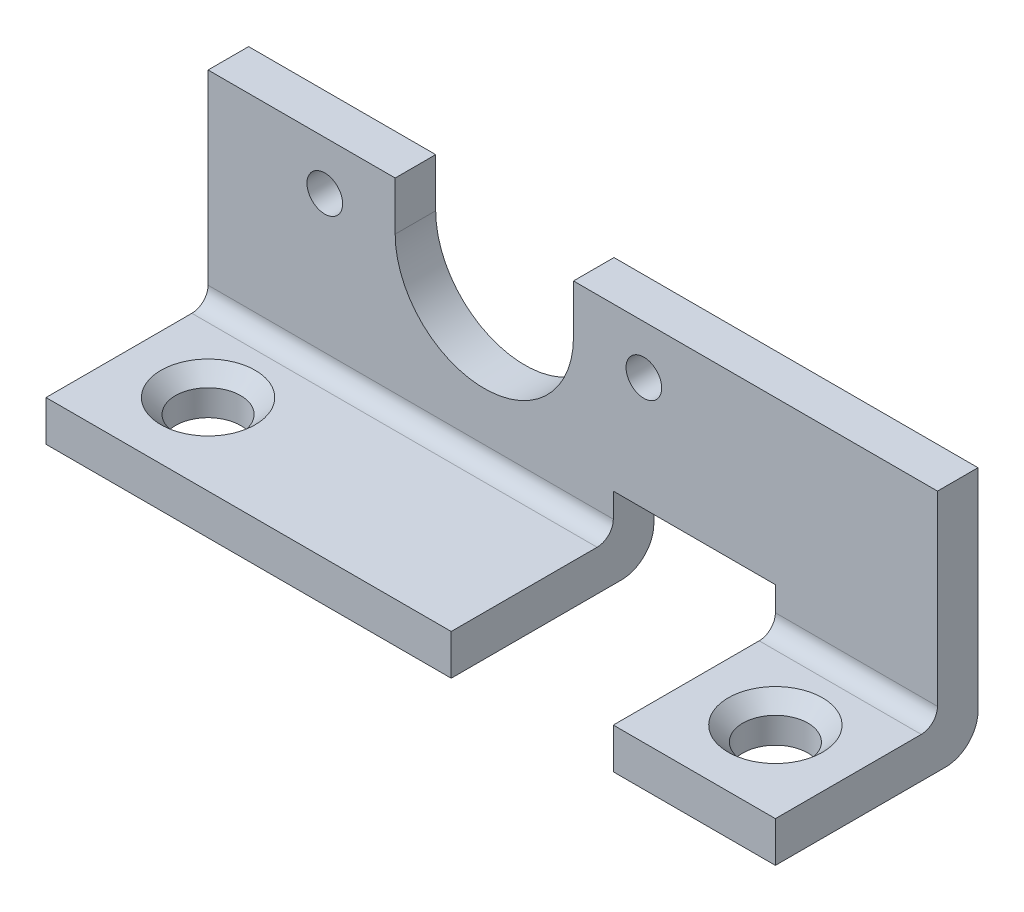
SolidWorks part; units mm, degrees
ref_plane "Front Plane" through (0, 0, 0) normal (0, 0, 1) x (1, 0, 0)
ref_plane "Top Plane" through (0, 0, 0) normal (0, 1, 0) x (1, 0, 0)
ref_plane "Right Plane" through (0, 0, 0) normal (1, 0, 0) x (0, 0, -1)
sketch "Sketch1" plane through (0, 0, 0) normal (0, 0, 1) x (1, 0, 0)
  line L0 (-13.916, 15.24) -> (-13.916, 19.05)
  line L1 (-28.575, 19.05) -> (-13.916, 19.05)
  line L2 (-28.575, 19.05) -> (-28.575, 0)
  line L3 (-28.575, 0) -> (28.575, 0)
  line L4 (28.575, 19.05) -> (28.575, 0)
  line L5 (-28.575, 19.05) -> (28.575, 0) construction
  line L6 (-28.575, 0) -> (28.575, 19.05) construction
  line L7 (0.054, 15.24) -> (0.054, 19.05)
  line L8 (5.569, 15.24) -> (-19.431, 15.24) construction
  line L9 (0.054, 19.05) -> (28.575, 19.05)
  arc A0 (-13.916, 15.24) -> (0.054, 15.24) centre (-6.931, 15.24) ccw
  circle A1 centre (5.569, 15.24) radius 1.397
  circle A2 centre (-19.431, 15.24) radius 1.397
  point P0 (0, 9.525)
  dimension "D3" = 13.97
  dimension "D5" = 2.794
  dimension "D1" = 57.15
  dimension "D2" = 19.05
  dimension "D4" = 3.81
  dimension "D6" = 25
  dimension "D8" = 9.144
extrude "Boss-Extrude1" add sketch "Sketch1" against normal blind 3.175
sketch "Sketch2" plane through (0, 0, 0) normal (0, 1, 0) x (1, 0, 0)
  line L0 (0, -12.7) -> (0, 0) construction
  line L1 (-28.575, -12.7) -> (28.575, -12.7)
  line L2 (-28.575, -12.7) -> (-28.575, 0)
  line L3 (-28.575, 0) -> (28.575, 0)
  line L4 (28.575, -12.7) -> (28.575, 0)
  line L5 (-28.575, -12.7) -> (28.575, 0) construction
  line L6 (-28.575, 0) -> (28.575, -12.7) construction
  circle A0 centre (-22.225, -6.35) radius 2.5527
  circle A1 centre (22.225, -6.35) radius 2.5527
  point P0 (0, -6.35)
  dimension "D2" = 5.1054
  dimension "D1" = 12.7
  dimension "D3" = 44.45
extrude "Boss-Extrude2" add sketch "Sketch2" along normal blind 3.175
fillet "Fillet1" radius 1.27 1 edges
fillet "Fillet2" radius 2.54 1 edges at (0, 0, -3.175)
chamfer "Chamfer1" distance 1.143 angle 45 2 edges at (-22.225, 3.175, 8.9027) (22.225, 3.175, 8.9027)
sketch "Sketch3" plane through (0, 0, -3.175) normal (0, 0, -1) x (-1, 0, 0)
  line L1 (-15.875, 0) -> (-3.175, 0)
  line L2 (-15.875, 0) -> (-15.875, 6.35)
  line L3 (-15.875, 6.35) -> (-3.175, 6.35)
  line L4 (-3.175, 0) -> (-3.175, 6.35)
  line L5 (-28.575, 2.54) -> (-28.575, 19.05) construction
  line L6 (28.575, 0) -> (-28.575, 0) construction
  point P4 (-9.525, 0)
  dimension "D1" = 19.05
  dimension "D2" = 12.7
  dimension "D3" = 6.35
extrude "Cut-Extrude1" cut sketch "Sketch3" against normal through all
